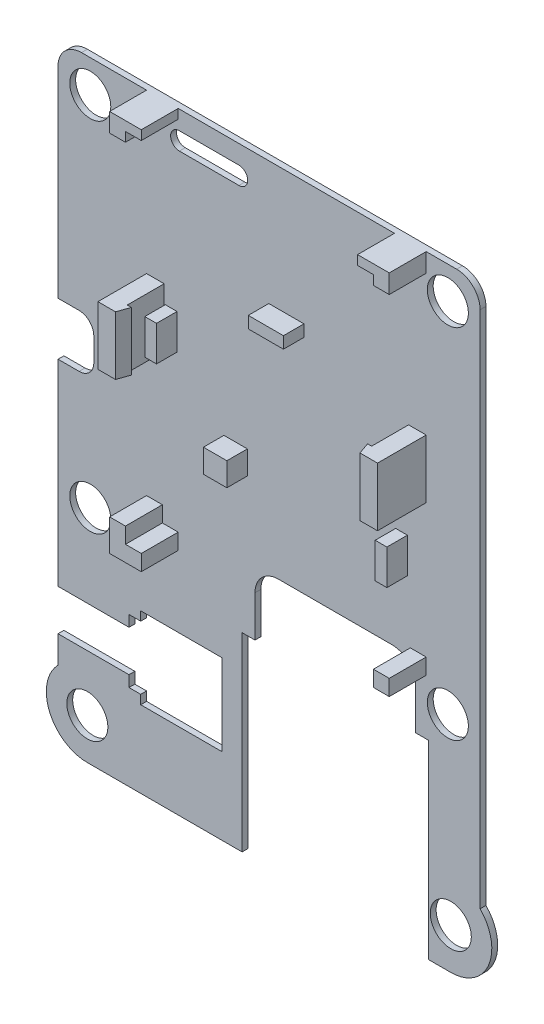
SolidWorks part; units mm, degrees
ref_plane "Front Plane" through (0, 0, 0) normal (0, 0, 1) x (1, 0, 0)
ref_plane "Top Plane" through (0, 0, 0) normal (0, 1, 0) x (1, 0, 0)
ref_plane "Right Plane" through (0, 0, 0) normal (1, 0, 0) x (0, 0, -1)
sketch "Sketch1" plane through (0, 0, 0) normal (0, 0, 1) x (1, 0, 0)
  line L9 (18, -18) -> (-18, -18)
  line L14 (16, 18) -> (-16, 18)
  line L15 (-18, 16) -> (-18, -1.15)
  line L16 (-18, -1.15) -> (-16.2, -1.15)
  line L17 (-14.95, -2.4) -> (-14.95, -4.4)
  line L18 (-16.2, -5.65) -> (-18, -5.65)
  line L19 (-18, -5.65) -> (-18, -18)
  line L20 (-18, -18) -> (-1.2, -18)
  line L21 (-1.2, -18) -> (-1.2, -14.5)
  line L22 (0.8, -12.5) -> (10.5, -12.5)
  line L23 (12.5, -14.5) -> (12.5, -18)
  line L24 (12.5, -18) -> (18, -18)
  line L25 (18, -18) -> (18, 16)
  line L26 (16, 18) -> (-16, 18)
  line L27 (-18, 16) -> (-18, -1.15)
  line L28 (-18, -1.15) -> (-16.2, -1.15)
  line L29 (-14.95, -2.4) -> (-14.95, -4.4)
  line L30 (-16.2, -5.65) -> (-18, -5.65)
  line L31 (-18, -5.65) -> (-18, -18)
  line L32 (-18, -18) -> (-1.2, -18)
  line L33 (-1.2, -18) -> (-1.2, -14.5)
  line L34 (0.8, -12.5) -> (10.5, -12.5)
  line L35 (12.5, -14.5) -> (12.5, -18)
  line L36 (12.5, -18) -> (18, -18)
  line L37 (18, -18) -> (18, 16)
  line L41 (13.6, -18) -> (13.6, -34.2)
  line L42 (13.6, -34.2) -> (15.5, -34.2)
  line L43 (18, -28.2505) -> (18, -18)
  line L44 (18, -18) -> (13.6, -18)
  line L46 (13.6, -18) -> (13.6, -34.2)
  line L47 (13.6, -34.2) -> (15.5, -34.2)
  line L48 (18, -28.2505) -> (18, -18)
  line L49 (18, -18) -> (13.6, -18)
  line L66 (-2.3, -18) -> (-18, -18)
  line L153 (-11.95, -22.43) -> (-11.95, -21.48)
  line L154 (-11.95, -21.48) -> (-10.95, -21.48)
  line L155 (-10.95, -21.48) -> (-10.95, -20.71)
  line L156 (-10.95, -20.71) -> (-4.01, -20.71)
  line L157 (-4.01, -20.71) -> (-4.01, -27.65)
  line L158 (-4.01, -27.65) -> (-10.95, -27.65)
  line L159 (-10.95, -27.65) -> (-10.95, -26.88)
  line L160 (-10.95, -26.88) -> (-11.95, -26.88)
  line L161 (-11.95, -26.88) -> (-11.95, -25.93)
  line L162 (-11.95, -25.93) -> (-18, -25.93)
  line L163 (-18, -25.93) -> (-18, -28.2505)
  line L164 (-15.5, -34.2) -> (-2.3, -34.2)
  line L165 (-2.3, -34.2) -> (-2.3, -18)
  line L166 (-2.3, -18) -> (-18, -18)
  line L167 (-18, -18) -> (-18, -22.43)
  line L168 (-18, -22.43) -> (-11.95, -22.43)
  line L169 (-11.95, -22.43) -> (-11.95, -21.48)
  line L170 (-11.95, -21.48) -> (-10.95, -21.48)
  line L171 (-10.95, -21.48) -> (-10.95, -20.71)
  line L172 (-10.95, -20.71) -> (-4.01, -20.71)
  line L173 (-4.01, -20.71) -> (-4.01, -27.65)
  line L174 (-4.01, -27.65) -> (-10.95, -27.65)
  line L175 (-10.95, -27.65) -> (-10.95, -26.88)
  line L176 (-10.95, -26.88) -> (-11.95, -26.88)
  line L177 (-11.95, -26.88) -> (-11.95, -25.93)
  line L178 (-11.95, -25.93) -> (-18, -25.93)
  line L179 (-18, -25.93) -> (-18, -28.2505)
  line L180 (-15.5, -34.2) -> (-2.3, -34.2)
  line L181 (-2.3, -34.2) -> (-2.3, -18)
  line L182 (-2.3, -18) -> (-18, -18)
  line L183 (-18, -18) -> (-18, -22.43)
  line L184 (-18, -22.43) -> (-11.95, -22.43)
  line L229 (-7.65, 14.9) -> (-2.57, 14.9) construction
  line L230 (-7.65, 16.4) -> (-2.57, 16.4) construction
  line L231 (-7.65, 16.4) -> (-2.57, 16.4)
  line L232 (-7.65, 14.9) -> (-2.57, 14.9)
  circle A2 centre (15.5, -30.7) radius 1.5 construction
  arc A3 (15.5, -34.2) -> (18, -28.2505) centre (15.5, -30.7) ccw
  circle A4 centre (15.25, -15.25) radius 1.75 construction
  circle A5 centre (15.25, 15.25) radius 1.75 construction
  circle A6 centre (-15.25, -15.25) radius 1.75 construction
  arc A7 (-16, 18) -> (-18, 16) centre (-16, 16) ccw
  arc A8 (-14.95, -2.4) -> (-16.2, -1.15) centre (-16.2, -2.4) ccw
  arc A9 (-16.2, -5.65) -> (-14.95, -4.4) centre (-16.2, -4.4) ccw
  arc A10 (0.8, -12.5) -> (-1.2, -14.5) centre (0.8, -14.5) ccw
  arc A11 (12.5, -14.5) -> (10.5, -12.5) centre (10.5, -14.5) ccw
  arc A12 (18, 16) -> (16, 18) centre (16, 16) ccw
  arc A14 (-16, 18) -> (-18, 16) centre (-16, 16) ccw
  arc A15 (-14.95, -2.4) -> (-16.2, -1.15) centre (-16.2, -2.4) ccw
  arc A16 (-16.2, -5.65) -> (-14.95, -4.4) centre (-16.2, -4.4) ccw
  arc A17 (0.8, -12.5) -> (-1.2, -14.5) centre (0.8, -14.5) ccw
  arc A19 (12.5, -14.5) -> (10.5, -12.5) centre (10.5, -14.5) ccw
  arc A20 (18, 16) -> (16, 18) centre (16, 16) ccw
  circle A21 centre (-15.25, 15.25) radius 1.75 construction
  arc A22 (15.5, -34.2) -> (18, -28.2505) centre (15.5, -30.7) ccw
  circle A23 centre (15.25, -15.25) radius 1.75
  circle A24 centre (15.25, 15.25) radius 1.75
  circle A25 centre (-15.25, -15.25) radius 1.75
  circle A26 centre (-15.25, 15.25) radius 1.75
  arc A27 (-18, -28.2505) -> (-15.5, -34.2) centre (-15.5, -30.7) ccw
  arc A28 (-18, -28.2505) -> (-15.5, -34.2) centre (-15.5, -30.7) ccw
  circle A36 centre (15.5, -30.7) radius 1.5
  circle A54 centre (-15.5, -30.7) radius 1.5 construction
  circle A57 centre (-15.5, -30.7) radius 1.5
  arc A62 (-2.57, 14.9) -> (-2.57, 16.4) centre (-2.57, 15.65) ccw construction
  arc A63 (-7.65, 16.4) -> (-7.65, 14.9) centre (-7.65, 15.65) ccw construction
  arc A64 (-7.65, 16.4) -> (-7.65, 14.9) centre (-7.65, 15.65) ccw
  arc A65 (-2.57, 14.9) -> (-2.57, 16.4) centre (-2.57, 15.65) ccw
  circle A69 centre (-15.5, -30.7) radius 1.75
  circle A70 centre (15.5, -30.7) radius 1.75
  dimension "D1" = 0
  dimension "D2" = 0
  dimension "D3" = 0
extrude "Base shape" add sketch "Sketch1" along normal blind 0.5 contours L37 A20 L26 A14 L27 L28 A15 L29 A16 L30 L31 L32 L33 A17 L34 A19 L35 L36 A26 A25 A24 A23 | L36 | L32 | L47 A22 L48 L9 L46 A36 region at (15.9615, -25.5534, 0) region at (-0.1312, 0.8573, 0) region at (-2.5327, -26.1, 0)
sketch "Sketch2" plane through (0, 0, 0.5) normal (0, 0, 1) x (1, 0, 0)
  line L0 (1.475, 16.95) -> (1.475, -13.05) construction
  line L1 (-7.85, 1.45) -> (-8.85, 1.45) construction
  line L2 (-0.025, 7.45) -> (2.975, 7.45)
  line L3 (-0.025, 7.45) -> (-0.025, 6.45)
  line L4 (11.8, 16.95) -> (-8.85, 16.95)
  line L5 (-8.85, 16.95) -> (-8.85, -13.05)
  line L6 (-8.85, -13.05) -> (11.8, -13.05)
  line L7 (11.8, -13.05) -> (11.8, 16.95)
  line L8 (11.8, 16.95) -> (-8.85, 16.95)
  line L9 (-8.85, 16.95) -> (-8.85, -13.05)
  line L10 (-8.85, -13.05) -> (11.8, -13.05)
  line L11 (11.8, -13.05) -> (11.8, 16.95)
  line L12 (-0.025, 6.45) -> (2.975, 6.45)
  line L13 (2.975, 7.45) -> (2.975, 6.45)
  line L14 (-0.025, 7.45) -> (2.975, 6.45) construction
  line L15 (-0.025, 6.45) -> (2.975, 7.45) construction
  line L16 (-8.85, 2.95) -> (-7.85, 2.95)
  line L17 (-8.85, 2.95) -> (-8.85, -0.05)
  line L18 (-8.85, -0.05) -> (-7.85, -0.05)
  line L19 (-7.85, 2.95) -> (-7.85, -0.05)
  line L20 (-3.85, -4.2) -> (-1.85, -4.2)
  line L21 (-3.85, -4.2) -> (-3.85, -6.2)
  line L22 (-3.85, -6.2) -> (-1.85, -6.2)
  line L23 (-1.85, -4.2) -> (-1.85, -6.2)
  line L24 (11.8, -3.75) -> (10.8, -3.75)
  line L25 (11.8, -3.75) -> (11.8, -6.75)
  line L26 (11.8, -6.75) -> (10.8, -6.75)
  line L27 (10.8, -3.75) -> (10.8, -6.75)
  line L28 (11.8, 1.95) -> (10.8, 1.95)
  line L29 (11.8, 1.95) -> (11.8, -1.05)
  line L30 (11.8, -1.05) -> (10.8, -1.05)
  line L31 (10.8, 1.95) -> (10.8, -1.05)
  line L32 (-3.85, -5.2) -> (-1.85, -5.2) construction
  line L33 (-2.85, -4.2) -> (-2.85, -6.2) construction
  line L34 (10.8, 0.45) -> (11.8, 0.45) construction
  line L35 (10.8, -5.25) -> (11.8, -5.25) construction
  point P6 (1.475, 6.95)
  dimension "D2" = 3
  dimension "D3" = 1
  dimension "D4" = 10
  dimension "D5" = 7.8
  dimension "D6" = 16.5
  dimension "D7" = 7.85
  dimension "D8" = 6
  dimension "D9" = 2
  dimension "D10" = 15.5
  dimension "D1" = 0
extrude "RX supports" add sketch "Sketch2" along normal blind 1.75 contours L13 L2 L3 L12 | L19 L16 L9 L18 | L23 L20 L21 L22 | L28 L31 L30 L11 | L24 L27 L26 L11 region at (1.475, 6.95, 0.5) region at (11.3, 0.45, 0.5) region at (-8.35, 1.45, 0.5) region at (11.3, -5.25, 0.5) region at (-2.85, -5.2, 0.5)
sketch "Sketch3" plane through (0, 0, 0.5) normal (0, 0, 1) x (1, 0, 0)
  line L0 (-8.85, 1.95) -> (11.8, 1.95) construction
  line L1 (1.475, 16.95) -> (1.475, -13.05) construction
  line L2 (-8.95, 4.45) -> (-10.45, 4.45)
  line L3 (-8.95, 4.45) -> (-8.95, -0.55)
  line L4 (11.8, 16.95) -> (-8.85, 16.95)
  line L5 (-8.85, 16.95) -> (-8.85, -13.05)
  line L6 (-8.85, -13.05) -> (11.8, -13.05)
  line L7 (11.8, -13.05) -> (11.8, 16.95)
  line L8 (11.8, 16.95) -> (-8.85, 16.95)
  line L9 (-8.85, 16.95) -> (-8.85, -13.05)
  line L10 (-8.85, -13.05) -> (11.8, -13.05)
  line L11 (11.8, -13.05) -> (11.8, 16.95)
  line L12 (-8.95, -0.55) -> (-10.45, -0.55)
  line L13 (-10.45, 4.45) -> (-10.45, -0.55)
  line L14 (11.9, -0.55) -> (13.4, -0.55)
  line L15 (13.4, 4.45) -> (13.4, -0.55)
  line L16 (11.9, 4.45) -> (13.4, 4.45)
  line L17 (11.9, 4.45) -> (11.9, -0.55)
  point P10 (-10.45, 1.95)
  dimension "D2" = 5
  dimension "D3" = 1.5
  dimension "D4" = 0.1
  dimension "D1" = 0
extrude "Clip base" add sketch "Sketch3" along normal offset from surface (3.15 mm away) 0.2 contours L2 L13 L12 L3 | L16 L17 L14 L15 region at (-9.7, 1.95, 0.5) region at (12.65, 1.95, 0.5) offset beyond the face yes
sketch "Sketch4" plane through (0, 0, 3.65) normal (0, 0, 1) x (1, 0, 0)
  line L0 (-8.95, -0.55) -> (-10.45, -0.55) construction
  line L1 (-10.45, 4.45) -> (-8.6, 4.45)
  line L2 (-10.45, 4.45) -> (-10.45, -0.55)
  line L3 (-10.45, -0.55) -> (-8.6, -0.55)
  line L4 (-8.6, 4.45) -> (-8.6, -0.55)
  line L5 (-8.95, 4.45) -> (-8.95, -0.55) construction
  line L6 (-10.45, 1.95) -> (13.4, 1.95) construction
  line L7 (13.4, 4.45) -> (13.4, -0.55) construction
  line L8 (1.475, 4.45) -> (1.475, -0.55) construction
  line L9 (11.55, 4.45) -> (11.55, -0.55)
  line L10 (13.4, 4.45) -> (11.55, 4.45)
  line L11 (13.4, 4.45) -> (13.4, -0.55)
  line L12 (13.4, -0.55) -> (11.55, -0.55)
  point P17 (1.475, 1.95)
  dimension "D1" = 0.35
extrude "Clip top" add sketch "Sketch4" along normal blind 1
sketch "Sketch5" plane through (0, -0.55, 0) normal (0, -1, 0) x (1, 0, 0)
  line L0 (-8.6, 3.65) -> (-8.95, 4.65)
  line L1 (-10.45, 4.65) -> (-8.6, 4.65) construction
  line L2 (-8.95, 4.65) -> (-8.6, 4.65)
  line L3 (-8.6, 4.65) -> (-8.6, 3.65)
  line L4 (-8.95, 3.65) -> (-8.95, 0.5) construction
  line L5 (11.55, 3.65) -> (11.9, 4.65)
  line L6 (11.55, 4.65) -> (13.4, 4.65) construction
  line L7 (11.9, 4.65) -> (11.55, 4.65)
  line L8 (11.55, 4.65) -> (11.55, 3.65)
  line L9 (11.9, 3.65) -> (11.9, 0.5) construction
extrude "Clip chamfer" cut sketch "Sketch5" against normal up to next
sketch "Sketch6" plane through (0, 0, 0.5) normal (0, 0, 1) x (1, 0, 0)
  line L0 (-10.45, 4.45) -> (-10.45, -0.55) construction
  line L1 (13.4, 4.45) -> (13.4, -0.55) construction
  line L2 (10.7, 18) -> (13.4, 18)
  line L3 (10.7, 18) -> (10.7, 16.4)
  line L4 (10.7, 16.4) -> (13.4, 16.4)
  line L5 (-7.75, -14.65) -> (-10.45, -14.65)
  line L6 (-7.75, -14.65) -> (-7.75, -11.95)
  line L7 (-7.75, -11.95) -> (-10.45, -11.95)
  line L8 (-9.1, -13.3) -> (12.05, -13.3)
  line L9 (12.05, -13.3) -> (12.05, 17.2)
  line L10 (12.05, 17.2) -> (-9.1, 17.2)
  line L11 (-9.1, 17.2) -> (-9.1, -13.3)
  line L12 (-9.1, -13.3) -> (12.05, -13.3)
  line L13 (12.05, -13.3) -> (12.05, 17.2)
  line L14 (12.05, 17.2) -> (-9.1, 17.2)
  line L15 (-9.1, 17.2) -> (-9.1, -13.3)
  line L16 (-10.45, -14.65) -> (-10.45, -11.95)
  line L17 (-7.75, -14.65) -> (-10.45, -11.95) construction
  line L18 (-7.75, -11.95) -> (-10.45, -14.65) construction
  line L19 (13.4, 18) -> (13.4, 16.4)
  line L20 (10.7, 18) -> (13.4, 16.4) construction
  line L21 (10.7, 16.4) -> (13.4, 18) construction
  line L22 (16, 18) -> (-16, 18) construction
  line L23 (-10.45, 4.45) -> (-10.45, -0.55) construction
  line L24 (-10.45, 16.4) -> (-7.75, 16.4)
  line L25 (-10.45, 16.4) -> (-10.45, 18)
  line L26 (-10.45, 18) -> (-7.75, 18)
  line L27 (-7.75, 16.4) -> (-7.75, 18)
  line L28 (-10.45, 16.4) -> (-7.75, 18) construction
  line L29 (-10.45, 18) -> (-7.75, 16.4) construction
  line L31 (12.05, -13.3) -> (13.4, -13.3)
  line L32 (12.05, -13.3) -> (12.05, -11.95)
  line L33 (12.05, -11.95) -> (13.4, -11.95)
  line L34 (13.4, -13.3) -> (13.4, -11.95)
  dimension "D1" = 0.25
extrude "Boss-Extrude1" add sketch "Sketch6" along normal up to surface (3.15 mm away) contours L14 L27 L26 L25 L24 L15 | L19 L2 L3 L14 L13 L4 | L31 L34 L33 L13 | L16 L5 L6 L12 L15 L7 region at (12.275, 17.3333, 0.5) region at (-9.325, 17.3333, 0.5) region at (12.725, -12.625, 0.5) region at (-9.325, -13.525, 0.5) up to face at (-8.775, 1.95, 3.65)
